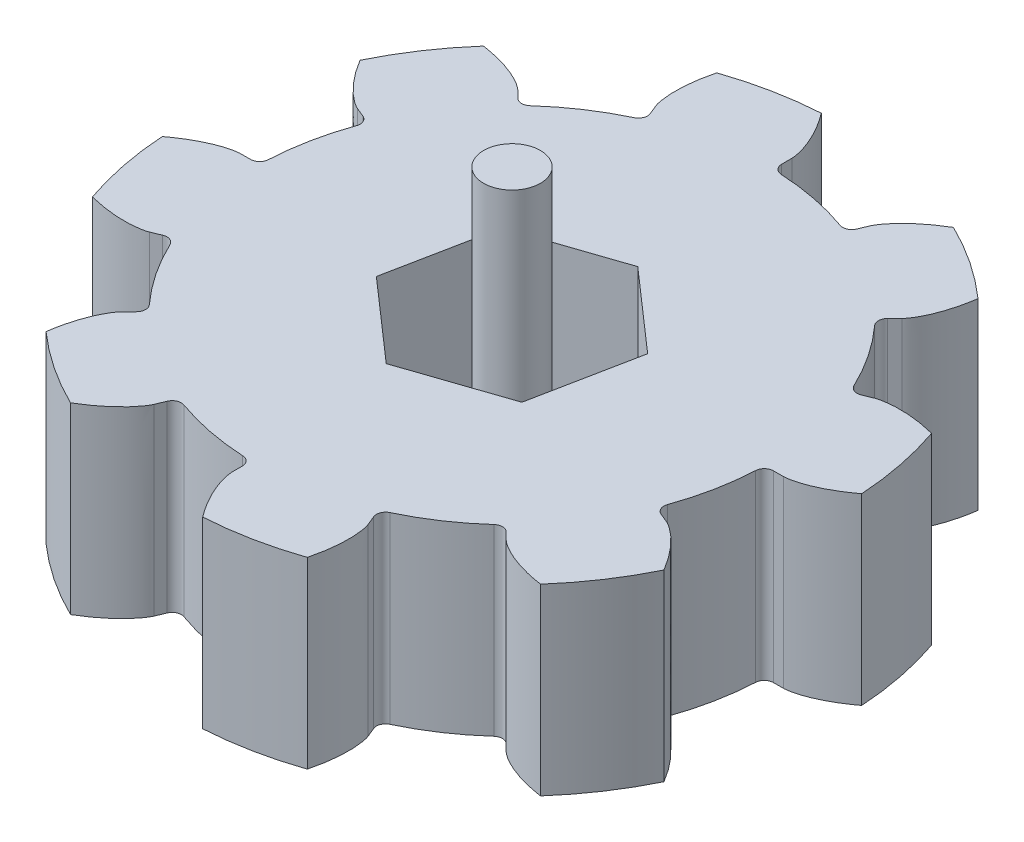
SolidWorks part; units mm, degrees
ref_plane "正面" through (0, 0, 0) normal (0, 0, 1) x (1, 0, 0)
ref_plane "平面" through (0, 0, 0) normal (0, 1, 0) x (1, 0, 0)
ref_plane "右側面" through (0, 0, 0) normal (1, 0, 0) x (0, 0, -1)
sketch "ｽｹｯﾁ1" plane through (0, 0, 0) normal (0, 1, 0) x (1, 0, 0)
  line L0 (0, 0) -> (0, 102.2347) construction
  line L1 (-97.1662, 16) -> (83.1097, 16) construction
  line L2 (-58.4661, -5.2799) -> (63.2436, 39.0188) construction
  circle A0 centre (0, 0) radius 16 construction
  circle A1 centre (0, 0) radius 15.0351 construction
  point P9 (0, 16)
  dimension "D2" = 32
  dimension "D1" = 20
sketch "ｽｹｯﾁ2" plane through (0, 0, 0) normal (0, 1, 0) x (1, 0, 0)
  line L0 (-5.1423, 14.1284) -> (0, 16) construction
  line L1 (-187996.9903, -68409.3086) -> (188001.7678, 68443.0475) construction
  line L2 (-4.3836, 14.3818) -> (0.0857, 15.7441) construction
  line L3 (-3.6125, 14.5946) -> (0.1463, 15.525) construction
  line L4 (-2.8312, 14.7661) -> (0.1861, 15.3446) construction
  line L5 (-2.0419, 14.8958) -> (0.2094, 15.2044) construction
  line L6 (-1.2468, 14.9833) -> (0.2205, 15.1054) construction
  line L7 (-0.4482, 15.0284) -> (0.2239, 15.0484) construction
  line L8 (-5.8864, 13.8349) -> (-0.1148, 16.2906) construction
  line L9 (-6.6139, 13.5022) -> (-0.2626, 16.6133) construction
  line L10 (-7.3226, 13.1314) -> (-0.4471, 16.9655) construction
  line L11 (-8.0106, 12.7233) -> (-0.6717, 17.3439) construction
  line L12 (-8.676, 12.2793) -> (-0.9398, 17.7453) construction
  line L13 (-9.3168, 11.8005) -> (-1.2544, 18.1659) construction
  line L14 (0, 0) -> (-6.4709, 32.5312) construction
  line L15 (0, -200000) -> (0, 200102.2347) construction
  circle A0 centre (0, 0) radius 15.0351 construction
  arc A1 (-5.1423, 14.1284) -> (-4.3836, 14.3818) centre (0, 0) cw
  arc A2 (-4.3836, 14.3818) -> (-3.6125, 14.5946) centre (0, 0) cw
  arc A3 (-3.6125, 14.5946) -> (-2.8312, 14.7661) centre (0, 0) cw
  arc A4 (-2.8312, 14.7661) -> (-2.0419, 14.8958) centre (0, 0) cw
  arc A5 (-2.0419, 14.8958) -> (-1.2468, 14.9833) centre (0, 0) cw
  arc A6 (-1.2468, 14.9833) -> (-0.4482, 15.0284) centre (0, 0) cw
  arc A7 (-5.1423, 14.1284) -> (-5.8864, 13.8349) centre (0, 0) ccw
  arc A8 (-5.8864, 13.8349) -> (-6.6139, 13.5022) centre (0, 0) ccw
  arc A9 (-6.6139, 13.5022) -> (-7.3226, 13.1314) centre (0, 0) ccw
  arc A10 (-7.3226, 13.1314) -> (-8.0106, 12.7233) centre (0, 0) ccw
  arc A11 (-8.0106, 12.7233) -> (-8.676, 12.2793) centre (0, 0) ccw
  arc A12 (-8.676, 12.2793) -> (-9.3168, 11.8005) centre (0, 0) ccw
  arc A13 (-5.1423, 14.1284) -> (0.2241, 15.0334) centre (0, 0) cw
  spline S0 degree 3 poles (-1.2544, 18.1659) (-1.0462, 17.9022) (-0.7654, 17.5086) (-0.4508, 16.9797) (-0.2659, 16.6275) (-0.1177, 16.3048) (-0.0025, 16.0142) (0.0836, 15.7583) (0.1447, 15.5393) (0.1848, 15.3589) (0.2085, 15.2186) (0.2204, 15.1146) (0.224, 15.0574) (0.2241, 15.0334) knots 0 0 0 0 0.287256 0.412688 0.52599 0.627162 0.716204 0.793115 0.857896 0.910546 0.951067 0.979456 1 1 1 1
  spline S1 degree 3 poles (-5.7929, 17.2632) (-5.8843, 16.9399) (-5.9931, 16.4688) (-6.0814, 15.8597) (-6.1175, 15.4636) (-6.1309, 15.1087) (-6.1261, 14.7961) (-6.1077, 14.5268) (-6.0803, 14.301) (-6.0483, 14.119) (-6.0165, 13.9804) (-5.9877, 13.8797) (-5.9692, 13.8255) (-5.9601, 13.8033) knots 0 0 0 0 0.287256 0.412688 0.52599 0.627162 0.716204 0.793115 0.857896 0.910546 0.951067 0.979456 1 1 1 1
  dimension "D1" = 5.4723
  dimension "D3" = 4.6723
  dimension "D4" = 3.8723
  dimension "D5" = 3.0723
  dimension "D6" = 2.2723
  dimension "D7" = 1.4723
  dimension "D8" = 0.6723
  dimension "D9" = 6.2723
  dimension "D10" = 7.0723
  dimension "D11" = 7.8723
  dimension "D12" = 8.6723
  dimension "D13" = 9.4723
  dimension "D14" = 10.2723
  dimension "D15" = 11.25
  dimension "D2" = 0.8
sketch "ｽｹｯﾁ3" plane through (0, 0, 0) normal (0, 1, 0) x (1, 0, 0)
  line L0 (0.2241, 15.0334) -> (0.2241, 13.9982)
  line L1 (0, 0) -> (-6.4709, 32.5312) construction
  line L2 (0, 0) -> (-6.4709, 32.5312) construction
  line L3 (-5.9601, 13.8033) -> (-5.5639, 12.8469)
  arc A0 (0.2241, 13.9982) -> (-5.5639, 12.8469) centre (0, 0) ccw
  arc A1 (-1.1008, 17.9663) -> (-5.8584, 17.02) centre (0, 0) ccw
  spline S0 degree 3 poles (-1.2544, 18.1659) (-1.0462, 17.9022) (-0.7654, 17.5086) (-0.4508, 16.9797) (-0.2659, 16.6275) (-0.1177, 16.3048) (-0.0025, 16.0142) (0.0836, 15.7583) (0.1447, 15.5393) (0.1848, 15.3589) (0.2085, 15.2186) (0.2204, 15.1146) (0.224, 15.0574) (0.2241, 15.0334) knots 0 0 0 0 0.287256 0.412688 0.52599 0.627162 0.716204 0.793115 0.857896 0.910546 0.951067 0.979456 1 1 1 1 construction
  spline S1 degree 3 poles (-5.7929, 17.2632) (-5.8843, 16.9399) (-5.9931, 16.4688) (-6.0814, 15.8597) (-6.1175, 15.4636) (-6.1309, 15.1087) (-6.1261, 14.7961) (-6.1077, 14.5268) (-6.0803, 14.301) (-6.0483, 14.119) (-6.0165, 13.9804) (-5.9877, 13.8797) (-5.9692, 13.8255) (-5.9601, 13.8033) knots 0 0 0 0 0.287256 0.412688 0.52599 0.627162 0.716204 0.793115 0.857896 0.910546 0.951067 0.979456 1 1 1 1 construction
  spline S2 degree 3 poles (-1.1008, 17.9663) (-0.9496, 17.7647) (-0.7225, 17.4365) (-0.4508, 16.9797) (-0.2659, 16.6275) (-0.1177, 16.3048) (-0.0025, 16.0142) (0.0836, 15.7583) (0.1447, 15.5393) (0.1848, 15.3589) (0.2085, 15.2186) (0.2204, 15.1146) (0.224, 15.0574) (0.2241, 15.0334) knots 0 0 0 0 0.232146 0.367277 0.48934 0.598334 0.694261 0.777119 0.846908 0.90363 0.947283 0.977868 1 1 1 1
  spline S3 degree 3 poles (-5.8584, 17.02) (-5.9209, 16.7758) (-6.0052, 16.3857) (-6.0814, 15.8597) (-6.1175, 15.4636) (-6.1309, 15.1087) (-6.1261, 14.7961) (-6.1077, 14.5268) (-6.0803, 14.301) (-6.0483, 14.119) (-6.0165, 13.9804) (-5.9877, 13.8797) (-5.9692, 13.8255) (-5.9601, 13.8033) knots 0 0 0 0 0.232146 0.367277 0.48934 0.598334 0.694261 0.777119 0.846908 0.90363 0.947283 0.977868 1 1 1 1
  point P4 (-5.8584, 17.02)
  point P6 (-1.1008, 17.9663)
  dimension "D1" = 28
  dimension "D2" = 4
sketch "ｽｹｯﾁ4" plane through (0, 0, 0) normal (0, 1, 0) x (1, 0, 0)
  circle A0 centre (0, 0) radius 14
  dimension "D1" = 28
extrude "ﾎﾞｽ - 押し出し1" add sketch "ｽｹｯﾁ4" along normal blind 10
extrude "ﾎﾞｽ - 押し出し2" add sketch "ｽｹｯﾁ3" along normal blind 10
fillet "ﾌｨﾚｯﾄ1" radius 0.5 2 edges at (-5.5639, 5, -12.8469) (0.2241, 5, -13.9982)
pattern_circular "円形ﾊﾟﾀｰﾝ1" count 8 over 360 about axis through (0, 10, 0) along (0, 1, 0) of "ﾎﾞｽ - 押し出し2", "ﾌｨﾚｯﾄ1"
sketch "ｽｹｯﾁ5" plane through (0, 10, 0) normal (0, 1, 0) x (1, 0, 0)
  line L0 (2.7313, 13.731) -> (-9751.7848, -49025.533) construction
  line L1 (1.1376, 5.7192) -> (-4.3842, 3.8448)
  line L2 (-4.3842, 3.8448) -> (-5.5218, -1.8744)
  line L3 (-5.5218, -1.8744) -> (-1.1376, -5.7192)
  line L4 (-1.1376, -5.7192) -> (4.3842, -3.8448)
  line L5 (4.3842, -3.8448) -> (5.5218, 1.8744)
  line L6 (5.5218, 1.8744) -> (1.1376, 5.7192)
  circle A0 centre (0, 0) radius 5.05 construction
  arc A1 (4.705, 13.1857) -> (0.6991, 13.9825) centre (0, 0) ccw construction
  arc A2 (-4.705, -13.1857) -> (-0.6991, -13.9825) centre (0, 0) ccw construction
  point P13 (2.7313, 13.731)
  point P19 (-2.7313, -13.731)
  dimension "D1" = 10.1
extrude "ｶｯﾄ - 押し出し1" cut sketch "ｽｹｯﾁ5" against normal offset from surface (8 mm away) 2 up to face at (0, 0, 0)
sketch "ｽｹｯﾁ6" plane through (0, 2, 0) normal (0, 1, 0) x (1, 0, 0)
  circle A0 centre (0, 0) radius 1.55
  dimension "D1" = 3.1
extrude "ﾎﾞｽ - 押し出し3" add sketch "ｽｹｯﾁ6" along normal blind 15 contours A0
equation "\"D3@ｽｹｯﾁ2\"=\"D1@ｽｹｯﾁ2\"-\"D2@ｽｹｯﾁ2\""
equation "\"D4@ｽｹｯﾁ2\"=\"D3@ｽｹｯﾁ2\"-\"D2@ｽｹｯﾁ2\""
equation "\"D5@ｽｹｯﾁ2\"=\"D4@ｽｹｯﾁ2\"-\"D2@ｽｹｯﾁ2\""
equation "\"D6@ｽｹｯﾁ2\"=\"D5@ｽｹｯﾁ2\"-\"D2@ｽｹｯﾁ2\""
equation "\"D7@ｽｹｯﾁ2\"=\"D6@ｽｹｯﾁ2\"-\"D2@ｽｹｯﾁ2\""
equation "\"D8@ｽｹｯﾁ2\"=\"D7@ｽｹｯﾁ2\"-\"D2@ｽｹｯﾁ2\""
equation "\"D9@ｽｹｯﾁ2\"=\"D1@ｽｹｯﾁ2\"+\"D2@ｽｹｯﾁ2\""
equation "\"D10@ｽｹｯﾁ2\"=\"D9@ｽｹｯﾁ2\"+\"D2@ｽｹｯﾁ2\""
equation "\"D11@ｽｹｯﾁ2\"=\"D10@ｽｹｯﾁ2\"+\"D2@ｽｹｯﾁ2\""
equation "\"D12@ｽｹｯﾁ2\"=\"D11@ｽｹｯﾁ2\"+\"D2@ｽｹｯﾁ2\""
equation "\"D13@ｽｹｯﾁ2\"=\"D12@ｽｹｯﾁ2\"+\"D2@ｽｹｯﾁ2\""
equation "\"D14@ｽｹｯﾁ2\"=\"D13@ｽｹｯﾁ2\"+\"D2@ｽｹｯﾁ2\""
equation "\"D15@ｽｹｯﾁ2\"=90/8"
